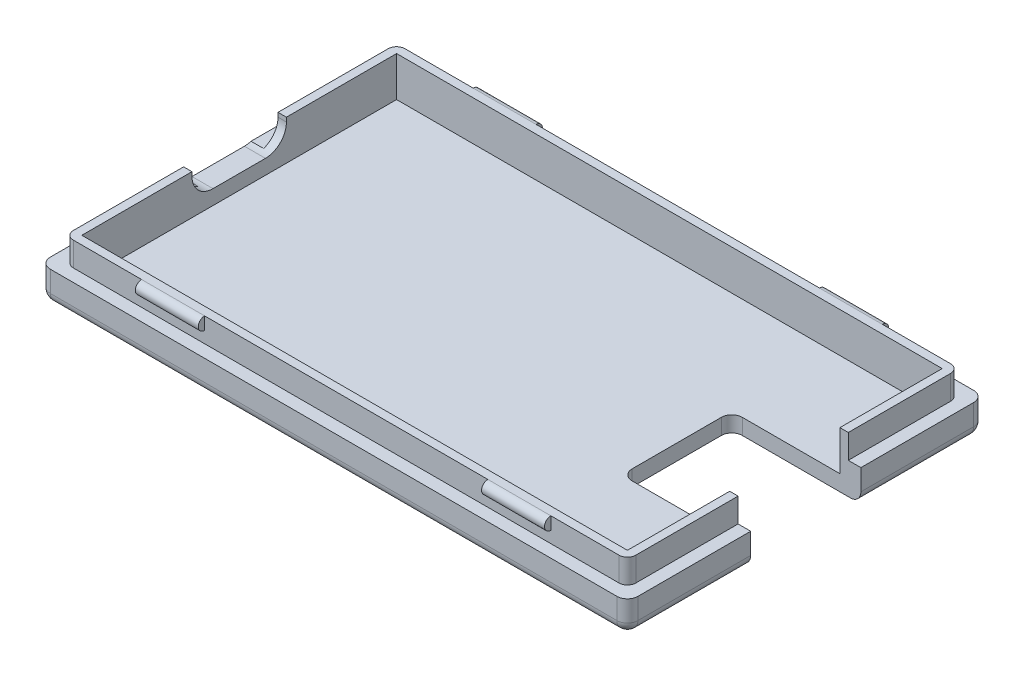
SolidWorks part; units mm, degrees
material "ABS"
ref_plane "Front Plane" through (0, 0, 0) normal (0, 0, 1) x (1, 0, 0)
ref_plane "Top Plane" through (0, 0, 0) normal (0, 1, 0) x (1, 0, 0)
ref_plane "Right Plane" through (0, 0, 0) normal (1, 0, 0) x (0, 0, -1)
sketch "Sketch1" plane through (0, 0, 0) normal (0, 1, 0) x (1, 0, 0)
  line L1 (28, -17) -> (-28, -17)
  line L2 (28, -17) -> (28, 17)
  line L3 (28, 17) -> (-28, 17)
  line L4 (-28, -17) -> (-28, 17)
  line L5 (28, -17) -> (-28, 17) construction
  line L6 (28, 17) -> (-28, -17) construction
  line L7 (26, -15) -> (-26, -15)
  line L8 (26, -15) -> (26, 15)
  line L9 (26, 15) -> (-26, 15)
  line L10 (-26, -15) -> (-26, 15)
  line L11 (26, -15) -> (-26, 15) construction
  line L12 (26, 15) -> (-26, -15) construction
  point P0 (0, 0)
  point P6 (0, 0)
  dimension "D1" = 56
  dimension "D2" = 34
  dimension "D3" = 2
  dimension "D4" = 2
extrude "Base" add sketch "Sketch1" along normal blind 1.5 contours L10 L7 L8 L9 | L4 L1 L2 L3 L7 L10 L9 L8 region at (0, 0, 16.3449) region at (0, 0, 0)
extrude "Boss-Extrude2" add sketch "Sketch1<3>" along normal blind 3 contours L4 L1 L2 L3 L7 L10 L9 L8 region at (0, 0, 16.3449)
sketch "Sketch1<3>" plane through (0, 0, 0) normal (0, 1, 0) x (1, 0, 0) same geometry as "Sketch1"
sketch "Sketch2" plane through (0, 3, 0) normal (0, 1, 0) x (1, 0, 0)
  line L0 (26, 15) -> (26, -15) construction
  line L1 (-26, -15) -> (26, -15) construction
  line L2 (-26, -15) -> (-26, 15) construction
  line L3 (-26, 15) -> (26, 15) construction
  line L4 (26, 15) -> (26, -15)
  line L5 (-26, -15) -> (26, -15)
  line L6 (-26, -15) -> (-26, 15)
  line L7 (-26, 15) -> (26, 15)
  line L8 (-26.8, 15.8) -> (26.8, 15.8)
  line L9 (26.8, 15.8) -> (26.8, -15.8)
  line L10 (-26.8, -15.8) -> (26.8, -15.8)
  line L11 (-26.8, -15.8) -> (-26.8, 15.8)
  dimension "D1" = 0.8
extrude "Wall" add sketch "Sketch2" along normal blind 2.3
sketch "Sketch3" plane through (0, 3, 0) normal (0, 1, 0) x (1, 0, 0)
  line L0 (-28, -17) -> (-28, 17) construction
  line L1 (-28, -10.25) -> (-26.8, -10.25)
  line L2 (-28, -10.25) -> (-28, -6.5)
  line L3 (-28, -6.5) -> (-26.8, -6.5)
  line L4 (-26.8, -10.25) -> (-26.8, -6.5)
  line L5 (-26.8, 15.8) -> (-26.8, -15.8) construction
  line L6 (0, 0) -> (-10.9883, 0) construction
  line L7 (-28, 6.5) -> (-26.8, 6.5)
  line L8 (-26.8, 10.25) -> (-26.8, 6.5)
  line L9 (-28, 10.25) -> (-26.8, 10.25)
  line L10 (-28, 10.25) -> (-28, 6.5)
  dimension "D1" = 13
  dimension "D2" = 20.5
extrude "GrooveForOpen" cut sketch "Sketch3" against normal blind 1
sketch "Sketch4" plane through (0, 0, 0) normal (1, 0, 0) x (0, 0, -1)
  line L0 (15.8, 5.3) -> (15.8, 3) construction
  line L1 (-15.8, 5.3) -> (-15.8, 3) construction
  circle A0 centre (15.8, 4.7) radius 0.6
  circle A1 centre (-15.8, 4.7) radius 0.6
  dimension "D1" = 1.2
extrude "LockPins" add sketch "Sketch4" along normal blind 6 from offset 13.5
mirror "LockPins2" about plane through (0, 0, 0) normal (1, 0, 0) of "LockPins"
fillet "FilletBase" radius 1 8 edges at (0, 0, 17) (28, 0, 0) (0, 0, -17) (-28, 0, 0) (28, 1.5, 17) (-28, 1.5, 17) (-28, 1.5, -17) (28, 1.5, -17)
fillet "FilletInner" radius 0.8 4 edges at (26.8, 4.15, 15.8) (-26.8, 4.15, 15.8) (-26.8, 4.15, -15.8) (26.8, 4.15, -15.8)
sketch "Sketch5" plane through (0, 0, 0) normal (1, 0, 0) x (0, 0, -1)
  line L0 (-15, 5.3) -> (15, 5.3) construction
  line L1 (-4.5, 5.4623) -> (4.5, 5.4623)
  line L2 (-4.5, 5.4623) -> (-4.5, 4.9)
  line L3 (-2.5, 2.9) -> (2.5, 2.9)
  line L4 (4.5, 5.4623) -> (4.5, 4.9)
  arc A0 (2.5, 2.9) -> (4.5, 4.9) centre (2.5, 4.9) ccw
  arc A1 (-4.5, 4.9) -> (-2.5, 2.9) centre (-2.5, 4.9) ccw
  point P4 (0, 5.4623)
  point P6 (0, 0)
  dimension "D2" = 2
  dimension "D1" = 9
  dimension "D3" = 2.4
extrude "CutCable" cut sketch "Sketch5" against normal through all
sketch "Sketch7" plane through (0, 0, 0) normal (0, -1, 0) x (1, 0, 0)
  line L0 (28, 16) -> (28, -16) construction
  line L1 (28.0151, -5.25) -> (16.7, -5.25)
  line L2 (28.0151, -5.25) -> (28.0151, 5.25)
  line L3 (28.0151, 5.25) -> (16.7, 5.25)
  line L4 (15.7, -4.25) -> (15.7, 4.25)
  line L5 (28.0151, -5.25) -> (15.7, 5.25) construction
  line L6 (28.0151, 5.25) -> (15.7, -5.25) construction
  arc A0 (16.7, -5.25) -> (15.7, -4.25) centre (16.7, -4.25) cw
  arc A1 (15.7, 4.25) -> (16.7, 5.25) centre (16.7, 4.25) cw
  point P0 (21.8576, 0)
  point P5 (22.1576, 0)
  dimension "D2" = 1
  dimension "D1" = 10.5
  dimension "D4" = 12.3
extrude "CutForConnector" cut sketch "Sketch7" against normal through all
